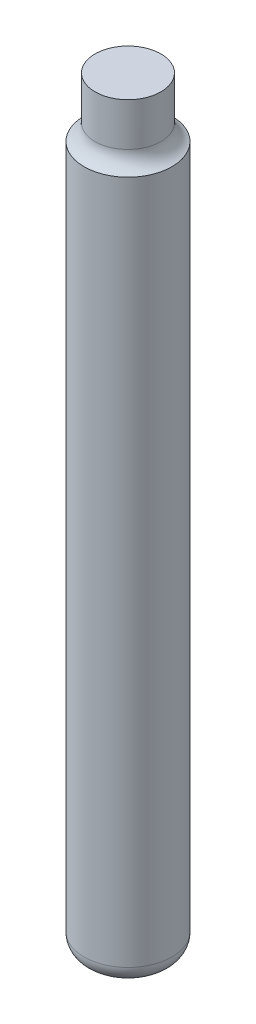
SolidWorks part; units mm, degrees
ref_plane "Front Plane" through (0, 0, 0) normal (0, 0, 1) x (1, 0, 0)
ref_plane "Top Plane" through (0, 0, 0) normal (0, 1, 0) x (1, 0, 0)
ref_plane "Right Plane" through (0, 0, 0) normal (1, 0, 0) x (0, 0, -1)
sketch "Sketch1" plane through (0, 0, 0) normal (0, 1, 0) x (1, 0, 0)
  circle A0 centre (0, 0) radius 3.175
  dimension "D1" = 6.35
extrude "Boss-Extrude1" add sketch "Sketch1" along normal blind 50.8
fillet "Fillet1" radius 1.27 1 edges at (0, 0, 3.175)
sketch "Sketch2" plane through (0, 0, 0) normal (0, 0, 1) x (1, 0, 0)
  line L1 (-20.8792, 55.096) -> (11.3459, 55.096) construction
  line L2 (0, 50.8) -> (0, 55.096)
  line L3 (3.175, 50.8) -> (-3.175, 50.8) construction
sketch "Sketch4" plane through (0, 50.8, 0) normal (0, 1, 0) x (1, 0, 0)
  circle A0 centre (0, 0) radius 2.3813
  dimension "D1" = 4.7625
sweep "Sweep1" add profiles "Sketch4" path "Sketch2"
fillet "Fillet2" radius 1.27 1 edges at (0, 50.8, 2.3813)
